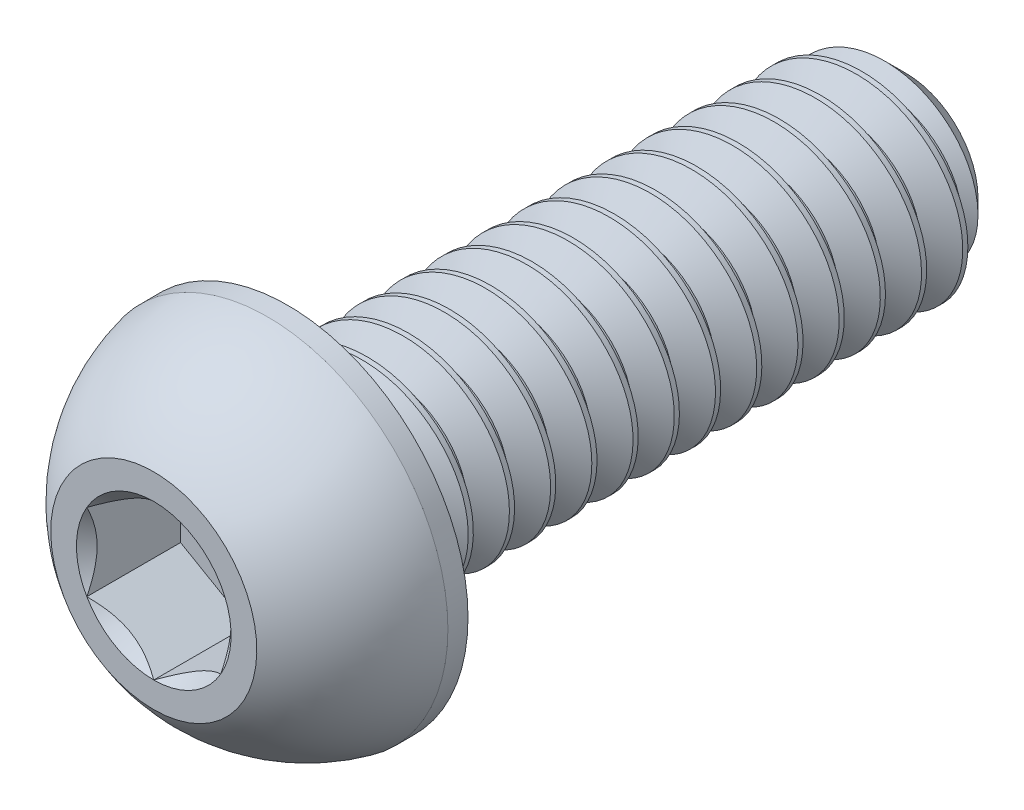
SolidWorks part; units mm, degrees
ref_plane "Front" through (0, 0, 0) normal (0, 0, 1) x (1, 0, 0)
ref_plane "Top" through (0, 0, 0) normal (0, 1, 0) x (1, 0, 0)
ref_plane "Right" through (0, 0, 0) normal (1, 0, 0) x (0, 0, -1)
sketch "Sketch1" plane through (0, 0, 0) normal (1, 0, 0) x (0, 0, -1)
  line L2 (1.3, 1) -> (7.3, 1)
  line L3 (7.3, 1) -> (7.3, 0)
  line L4 (7.3, 0) -> (1.3, 0)
  line L6 (1.105, 1.75) -> (1.3, 1.75) construction
  line L7 (7.3, 1) -> (7.3, -1) construction
  line L8 (0, 0) -> (1.3, 0) construction
  line L9 (1.3, 1.75) -> (1.3, -1.75) construction
  line L11 (1.3, 1) -> (1.3, 0)
  line L13 (0, 0.65) -> (0, -0.65) construction
  line L14 (0, 0.65) -> (0, 1) construction
  arc A3 (0, 1) -> (1.105, 1.75) centre (1.4858, 0) cw construction
  dimension "D1" = 0.195
revolve "Revolve1" add sketch "Sketch1" angle 360 mid plane about L4
sketch "Sketch3" plane through (0, 0, -7.3) normal (0, 0, -1) x (-1, 0, 0)
  circle A0 centre (0, 0) radius 1
curve "Helix/Spiral1" pitch 0.4 height 6.4 radius 1 centre (0, 0, -7.3) axis (0, 0, 1) start towards (1, 0, 0)
sketch "Sketch2" plane through (0, 0, 0) normal (1, 0, 0) x (0, 0, -1)
  line L0 (7.2, 1) -> (7.55, 1) construction
  line L1 (7.55, 1) -> (7.375, 0.6969) construction
  line L2 (7.375, 0.6969) -> (7.2, 1) construction
  line L3 (7.275, 0.8701) -> (7.475, 0.8701) construction
  line L4 (7.35, 0.7402) -> (7.4, 0.7402) construction
  line L5 (7.375, 0.7402) -> (7.375, 1) construction
  line L6 (7.2, 1) -> (7.55, 1)
  line L7 (7.55, 1) -> (7.4, 0.7402)
  line L8 (7.4, 0.7402) -> (7.35, 0.7402)
  line L9 (7.35, 0.7402) -> (7.2, 1)
  point P9 (7.375, 0.8701)
  dimension "D1" = 0.2
  dimension "D2" = 0.05
chamfer "Chamfer1" distance 0.3 angle 45 1 edges at (0, 1, -7.3)
sweep "Cut-Sweep1" cut profiles "Sketch2" path "Helix/Spiral1" align with end faces yes
sketch "Sketch7" plane through (0, 0, 0) normal (1, 0, 0) x (0, 0, -1)
  line L6 (1.105, 1.75) -> (1.3, 1.75) construction
  line L8 (0, 0) -> (1.3, 0) construction
  line L11 (1.3, 1.75) -> (1.3, -1.75) construction
  line L12 (1.105, 1.75) -> (1.3, 1.75)
  line L13 (0, 0) -> (1.3, 0)
  line L14 (0, 0.65) -> (0, -0.65) construction
  line L15 (1.3, 1.75) -> (1.3, 0)
  line L16 (0, 1) -> (0, 0)
  arc A2 (1.105, 1.75) -> (0, 1) centre (1.4858, 0) ccw construction
  arc A3 (1.105, 1.75) -> (0, 1) centre (1.4858, 0) ccw
revolve "Revolve2" add sketch "Sketch7" angle 360 mid plane about L13
sketch "Sketch5" plane through (0, 0, 0) normal (0, 0, 1) x (1, 0, 0)
  line L1 (0.65, -0.3753) -> (0.65, 0.3753)
  line L2 (0.65, 0.3753) -> (0, 0.7506)
  line L3 (0, 0.7506) -> (-0.65, 0.3753)
  line L4 (-0.65, 0.3753) -> (-0.65, -0.3753)
  line L5 (-0.65, -0.3753) -> (0, -0.7506)
  line L6 (0, -0.7506) -> (0.65, -0.3753)
  circle A0 centre (0, 0) radius 0.65 construction
extrude "Cut-Extrude2" cut sketch "Sketch5" against normal blind 0.91
sketch "Sketch6" plane through (0, 0, 0) normal (0, 0, 1) x (1, 0, 0)
  circle A0 centre (0, 0) radius 0.7506
extrude "Cut-Extrude3" cut sketch "Sketch6" against normal blind 0.91 draft 45
sketch "Sketch9" [suppressed] plane through (0, 0, -5.0546) normal (0, 0, 1) x (1, 0, 0)
  circle A2 centre (0, 0) radius 4.7625
extrude "Boss-Extrude2" [suppressed] add sketch "Sketch9" against normal offset from surface (6.35 mm away) 31.75 up to face at (0, 0.7, -7.3)
sketch "Sketch10" plane through (0, 0, 0) normal (1, 0, 0) x (0, 0, -1)
  line L0 (7.3, 1) -> (7.3, -1) construction
  point P0 (6.7, -1)
  dimension "D1" = 0.6
equation "\"D3@Helix/Spiral1\"=\"Lg@Sketch1\" + (\"D4@Helix/Spiral1\")"
equation "\"D1@Chamfer1\" = \"D4@Helix/Spiral1\" * .75"
equation "\"D1@Cut-Extrude2\" = \"Head Ht@Sketch1\" * .7"
equation "\"D1@Sketch1\" = \"Head Ht@Sketch1\" * .15"
equation "\"D1@Sketch10\" = \"D4@Helix/Spiral1\" * 1.5"
equation "\"D1@Cut-Extrude3\" = \"D1@Cut-Extrude2\""
equation "\"D1@Sketch2\"=\"D4@Helix/Spiral1\"*.5"
equation "\"D2@Sketch2\"=\"D4@Helix/Spiral1\"*.125"
